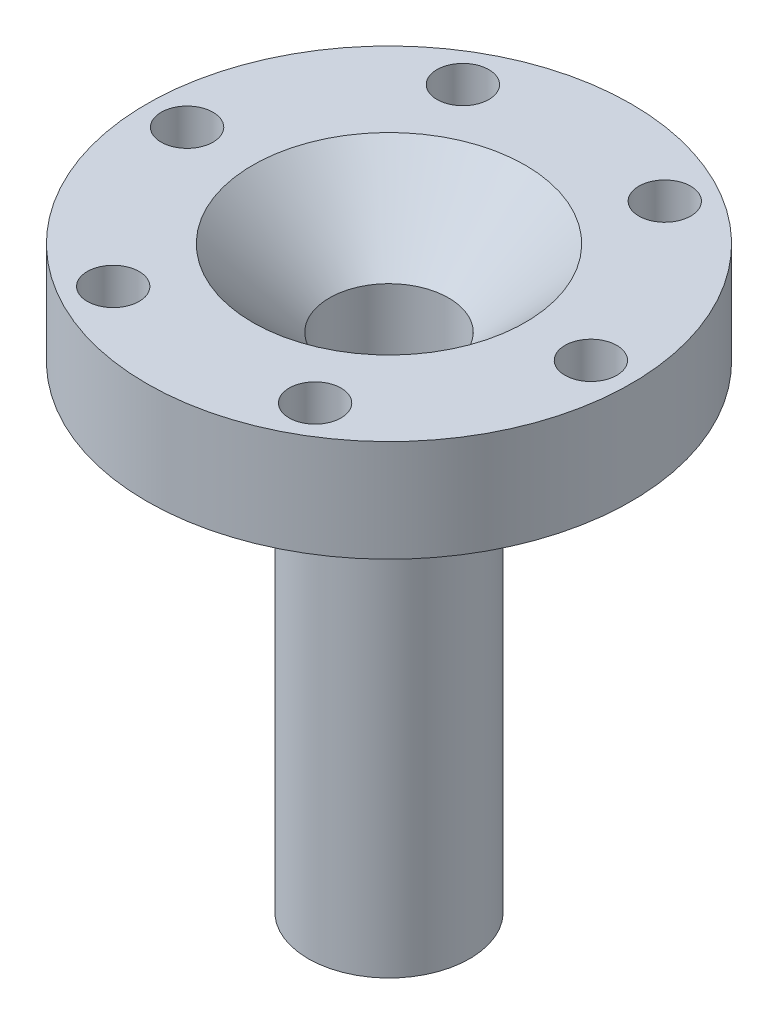
SolidWorks part; units mm, degrees
material "AISI Type 316L stainless steel"
ref_plane "Front Plane" through (0, 0, 0) normal (0, 0, 1) x (1, 0, 0)
ref_plane "Top Plane" through (0, 0, 0) normal (0, 1, 0) x (1, 0, 0)
ref_plane "Right Plane" through (0, 0, 0) normal (1, 0, 0) x (0, 0, -1)
sketch "Sketch1" plane through (0, 0, 0) normal (0, 0, 1) x (1, 0, 0)
  line L0 (0, 0) -> (0, -29.8554) construction
  line L1 (7.5, -72.82) -> (7.5, -9.645)
  line L2 (7.5, -9.645) -> (17.145, 0)
  line L3 (17.145, 0) -> (30.48, 0)
  line L4 (30.48, 0) -> (30.48, -12.82)
  line L5 (30.48, -12.82) -> (10.16, -12.82)
  line L6 (10.16, -12.82) -> (10.16, -72.82)
  line L7 (10.16, -72.82) -> (7.5, -72.82)
  dimension "D1" = 20.32
  dimension "D2" = 15
  dimension "D3" = 60
  dimension "D4" = 45
  dimension "D5" = 34.29
  dimension "D6" = 60.96
  dimension "D7" = 3.175
revolve "Revolve1" add sketch "Sketch1" angle 360 about L0
hole_wizard "1/4 Clearance Hole1" positions "Sketch3" profile "Sketch4" hole size "1/4" standard "ANSI Inch" end condition through all
sketch "Sketch3" plane through (0, 0, 0) normal (0, 1, 0) x (1, 0, 0)
  line L0 (25.4, 0) -> (0, 0) construction
  point P0 (25.4, 0)
  dimension "D1" = 25.4
sketch "Sketch4" plane through (25.4, 0, 0) normal (1, 0, 0) x (0, 0, 1)
  line L0 (0, 0) -> (0, 72.82)
  line L1 (0, 72.82) -> (3.2639, 72.82)
  line L2 (3.2639, 72.82) -> (3.2639, 0)
  line L5 (3.2639, 0) -> (0, 0)
  line L11 (0, -6.35) -> (0, 107.95) construction
  dimension "Thru Hole Dia." = 6.5278
  dimension "Thru Hole Depth" = 72.82
pattern_circular "CirPattern1" count 6 over 360 about axis through (0, 0, 0) along (0, 1, 0) of "1/4 Clearance Hole1" reverse direction yes
